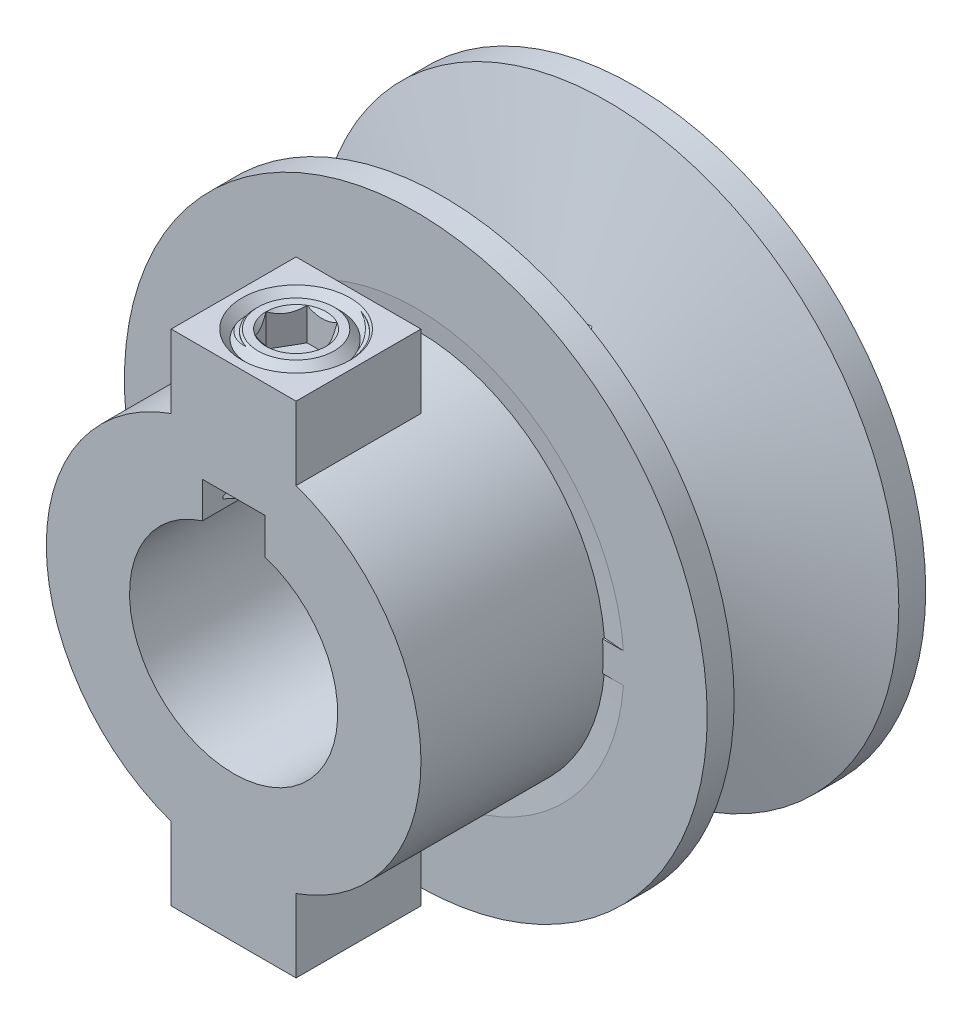
SolidWorks part; units mm, degrees
ref_plane "Front Plane" through (0, 0, 0) normal (0, 0, 1) x (1, 0, 0)
ref_plane "Top Plane" through (0, 0, 0) normal (0, 1, 0) x (1, 0, 0)
ref_plane "Right Plane" through (0, 0, 0) normal (1, 0, 0) x (0, 0, -1)
sketch "Sketch1" plane through (0, 0, 0) normal (1, 0, 0) x (0, 0, -1)
  line L0 (-22.225, 0) -> (8.3312, 0) construction
  line L1 (-6.2793, 22.225) -> (6.2793, 22.225) construction
  line L2 (6.2793, 22.225) -> (8.3312, 22.225)
  line L5 (-8.3312, 22.225) -> (6.2793, 22.225) construction
  line L7 (-22.225, 14.2875) -> (-22.225, -14.2875) construction
  line L10 (-8.3312, 15.875) -> (-8.1923, 14.2875)
  line L13 (-6.2793, 22.225) -> (-2.3965, 9.525)
  line L14 (-2.3965, 9.525) -> (2.3965, 9.525)
  line L15 (2.3965, 9.525) -> (6.2793, 22.225)
  line L16 (8.3312, 7.9375) -> (-22.225, 7.9375) construction
  line L17 (0, 22.225) -> (0, 0) construction
  line L18 (-6.2793, 22.225) -> (-8.3312, 22.225)
  line L20 (-22.225, 0) -> (-22.225, 7.9375) construction
  line L22 (5.3086, 19.05) -> (-5.3086, 19.05) construction
  line L23 (8.3312, 22.225) -> (8.3312, 0) construction
  line L24 (8.3312, 15.875) -> (8.1923, 14.2875)
  line L26 (-22.225, 14.2875) -> (-8.7312, 14.2875)
  line L27 (-8.7312, 14.2875) -> (8.3312, 14.2875) construction
  line L28 (-8.3312, 19.05) -> (-5.3086, 19.05) construction
  line L31 (-22.225, 14.2875) -> (-22.225, 0)
  line L32 (-8.3312, 15.875) -> (-8.3312, 22.225)
  line L33 (8.3312, 22.225) -> (8.3312, 15.875)
  line L34 (-22.225, 0) -> (8.3312, 0)
  line L35 (8.3312, 0) -> (8.3312, 14.2875)
  line L37 (-8.1923, 14.2875) -> (8.1923, 14.2875) construction
  line L39 (-8.7312, 14.2875) -> (-8.1923, 14.2875)
  line L40 (8.3312, 14.2875) -> (8.1923, 14.2875)
  line L42 (-8.7312, 14.2875) -> (-8.7312, 0) construction
  point P6 (0, 14.2875)
  point P16 (0, 9.525)
  point P25 (-8.7312, 0)
  dimension "D1" = 5
revolve "Revolve1" add sketch "Sketch1" angle 360 about L0
sketch "Sketch2" plane through (0, 0, 0) normal (0, 1, 0) x (0, 0, -1)
  line L0 (-6.2793, 22.225) -> (-8.3312, 22.225) construction
  line L1 (-8.3312, 22.225) -> (-8.3312, -22.225) construction
  line L4 (-8.1701, 14.0335) -> (-8.3312, 15.875)
  line L5 (-8.1923, 14.2875) -> (-22.225, 14.2875) construction
  line L6 (-8.3312, 14.0335) -> (-8.1701, 14.0335)
  line L7 (-8.3312, 14.0335) -> (-8.3312, 15.875)
  line L8 (-8.1923, 14.2875) -> (-8.3312, 15.875) construction
  line L11 (8.3312, 14.0335) -> (8.1701, 14.0335)
  line L12 (8.1701, 14.0335) -> (8.3312, 15.875)
  line L13 (0, 0) -> (0, 22.225) construction
  line L14 (8.3312, 14.0335) -> (8.3312, 15.875)
  dimension "D1" = 0.254
extrude "Boss-Extrude1" add sketch "Sketch2" along normal mid plane 2.286
pattern_circular "CirPattern1" count 2 over 360 of "Boss-Extrude1"
sketch "Sketch3" plane through (0, 0, -8.3312) normal (0, 0, -1) x (-1, 0, 0)
  circle A0 centre (0, 0) radius 7.9375
  circle A1 centre (0, 0) radius 19.05 construction
  point P4 (0, 7.9375)
extrude "Cut-Extrude1" cut sketch "Sketch3" against normal up to vertex (30.5562 mm away) up to point (0, 0, 22.225)
sketch "Sketch4" plane through (0, 0, -8.3312) normal (0, 0, -1) x (-1, 0, 0)
  line L0 (2.3812, 7.9375) -> (-2.3812, 7.9375) construction
  line L1 (2.3813, 10.3187) -> (-2.3813, 10.3187)
  line L2 (2.3813, 10.3187) -> (2.3812, 5.5562)
  line L3 (2.3812, 5.5562) -> (-2.3812, 5.5562)
  line L4 (-2.3813, 10.3187) -> (-2.3812, 5.5562)
  dimension "Keyway Wd." = 4.7625
  dimension "Keyway Dp." = 2.3813
extrude "Cut-Extrude2" cut sketch "Sketch4" against normal up to vertex (30.5562 mm away) up to point (0, 0, 22.225)
ref_plane "Plane1" through (0, 14.2875, 0) normal (0, 1, 0) x (-1, 0, 0)
sketch "Sketch5" plane through (0, 14.2875, 0) normal (0, 1, 0) x (-1, 0, 0)
  line L0 (0, 22.225) -> (0, 0) construction
  line L1 (4.7625, 12.7) -> (-4.7625, 12.7)
  line L2 (4.7625, 12.7) -> (4.7625, 22.225)
  line L3 (4.7625, 22.225) -> (-4.7625, 22.225)
  line L4 (-4.7625, 12.7) -> (-4.7625, 22.225)
  line L5 (14.2875, 22.225) -> (-14.2875, 22.225) construction
  dimension "D1" = 9.525
extrude "Boss-Extrude2" add sketch "Sketch5" against normal up to surface (5.5796 mm away) from offset 4.7625
mirror "Mirror1" about plane through (0, 0, 0) normal (0, 1, 0) of "Boss-Extrude2"
sketch "Sketch6" plane through (0, 19.05, 0) normal (0, 1, 0) x (-1, 0, 0)
  line L0 (0, 12.7) -> (0, 22.225) construction
  line L1 (4.7625, 22.225) -> (-4.7625, 22.225) construction
  line L2 (-4.7625, 12.7) -> (4.7625, 12.7) construction
  line L7 (0, 21.4312) -> (0, 20.0201) construction
  circle A0 centre (0, 17.4625) radius 3.9688 construction
  circle A1 centre (0, 17.4625) radius 3.0868
  dimension "D3" = 0.8819
extrude "Cut-Extrude3" cut sketch "Sketch6" against normal up to vertex (19.05 mm away) up to point (0, 0, 22.225)
sketch "Sketch7" plane through (0, 19.05, 0) normal (0, 1, 0) x (-1, 0, 0)
  circle A0 centre (0, 17.4625) radius 3.9688 construction
  circle A1 centre (0, 17.4625) radius 3.9688
  point P3 (0, 21.4312)
curve "Helix/Spiral1" pitch 1.4111 height 15.6986 turns 11.125
sketch "Sketch8" plane through (0, 0, 0) normal (1, 0, 0) x (0, 0, -1)
  line L0 (-20.3619, 20.4611) -> (-20.3619, 19.05) construction
  line L1 (-20.3619, 19.05) -> (-21.584, 19.7556) construction
  line L2 (-21.584, 19.7556) -> (-20.3619, 20.4611) construction
  line L3 (-20.3619, 19.05) -> (-21.4312, 19.05) construction
  line L4 (-21.4312, 19.05) -> (-21.4312, 19.6674) construction
  line L5 (-21.4312, 19.6674) -> (-21.4312, 19.8438) construction
  line L6 (-20.5147, 19.1382) -> (-20.5147, 20.3729) construction
  line L7 (-21.584, 19.7556) -> (-21.4312, 19.7556) construction
  line L8 (-20.5147, 19.7556) -> (-20.3619, 19.7556) construction
  line L9 (-20.4383, 20.417) -> (-20.4383, 19.0941)
  line L10 (-20.4383, 19.0941) -> (-21.4312, 19.6674)
  line L11 (-21.4312, 19.6674) -> (-21.4312, 19.8438)
  line L12 (-21.4312, 19.8438) -> (-20.4383, 20.417)
  point P16 (-20.4383, 19.7556)
  dimension "D1" = 1.4111
  dimension "D2" = 0.1764
sweep "Cut-Sweep1" cut profiles "Sketch8" path "Helix/Spiral1" align with end faces yes
sketch "Sketch9" plane through (0, 19.05, 0) normal (0, 1, 0) x (-1, 0, 0)
  circle A0 centre (0, 17.4625) radius 4.1215
extrude "Cut-Extrude4" cut sketch "Sketch9" against normal through all draft 45
sketch "Sketch10" plane through (0, 0, 0) normal (1, 0, 0) x (0, 0, -1)
  line L0 (-17.4625, 19.05) -> (-17.4625, 9.525) construction
  line L1 (-21.4312, 10.5943) -> (-21.4312, 17.9807)
  line L2 (-17.4625, 19.05) -> (-21.4312, 19.05) construction
  line L3 (-17.4625, 19.05) -> (-17.4625, 9.525)
  line L4 (-17.4625, 9.525) -> (-21.4312, 9.525) construction
  line L5 (-21.4312, 19.05) -> (-21.4312, 9.525) construction
  line L6 (-20.3619, 19.05) -> (-21.4312, 17.9807)
  line L7 (-21.4312, 10.5943) -> (-20.3619, 9.525)
  line L8 (-20.3619, 19.05) -> (-17.4625, 19.05)
  line L9 (-20.3619, 9.525) -> (-17.4625, 9.525)
  line L10 (-12.7, 19.05) -> (-22.225, 19.05) construction
  line L11 (-20.3619, 19.05) -> (-21.4312, 19.05) construction
  line L12 (-21.4312, 19.05) -> (-21.4312, 17.9807) construction
revolve "Revolve3" add sketch "Sketch10" angle 360 about L0
sketch "Sketch11" plane through (0, 19.05, 0) normal (0, 1, 0) x (-1, 0, 0)
  circle A1 centre (0, 17.4625) radius 3.9688
  circle A2 centre (0, 17.4625) radius 3.9688
  dimension "D1" = 0
curve "Helix/Spiral2" pitch 1.4111 height 10.9361 turns 7.75
sketch "Sketch12" plane through (0, 0, 0) normal (1, 0, 0) x (0, 0, -1)
  line L0 (-21.5076, 19.7115) -> (-21.5076, 18.3885)
  line L1 (-21.5076, 19.7556) -> (-21.5076, 19.7115) construction
  line L2 (-21.584, 19.7556) -> (-21.4312, 19.7556) construction
  line L3 (-20.3619, 19.05) -> (-21.584, 19.7556) construction
  line L4 (-21.5076, 19.7115) -> (-20.5147, 19.1382)
  line L5 (-20.5147, 19.1382) -> (-20.5147, 18.9618)
  line L6 (-20.5147, 18.9618) -> (-21.5076, 18.3885)
  line L7 (-21.584, 19.7556) -> (-20.3619, 19.05) construction
  line L8 (-20.3619, 19.05) -> (-21.584, 18.3444) construction
  line L9 (-21.584, 18.3444) -> (-21.584, 19.7556) construction
sweep "Cut-Sweep2" cut profiles "Sketch12" path "Helix/Spiral2" align with end faces yes
sketch "Sketch13" plane through (0, 19.05, 0) normal (0, 1, 0) x (1, 0, 0)
  line L1 (2.2914, -17.4625) -> (1.1457, -15.4781)
  line L2 (1.1457, -15.4781) -> (-1.1457, -15.4781)
  line L3 (-1.1457, -15.4781) -> (-2.2914, -17.4625)
  line L4 (-2.2914, -17.4625) -> (-1.1457, -19.4469)
  line L5 (-1.1457, -19.4469) -> (1.1457, -19.4469)
  line L6 (1.1457, -19.4469) -> (2.2914, -17.4625)
  circle A0 centre (0, -17.4625) radius 1.9844 construction
  dimension "D1" = 3.9688
extrude "Cut-Extrude5" cut sketch "Sketch13" against normal blind 2.4805
sketch "Sketch14" plane through (0, 19.05, 0) normal (0, 1, 0) x (1, 0, 0)
  circle A0 centre (0, -17.4625) radius 2.2914
extrude "Cut-Extrude6" cut sketch "Sketch14" against normal through all draft 45
equation "\"D3@Sketch6\" = \"Screw Pitch@Sketch6\" * 5 / 8"
equation "\"D4@Helix/Spiral1\" = \"Screw Pitch@Sketch6\""
equation "\"D3@Helix/Spiral1\" = \"D4@Helix/Spiral1\" + ( \"Hub Dia.@Sketch1\" / 2 ) "
equation "\"D1@Sketch8\" = \"D4@Helix/Spiral1\""
equation "\"D2@Sketch8\" = \"D1@Sketch8\" / 8"
equation "\"D4@Helix/Spiral2\" = \"D4@Helix/Spiral1\""
equation "\"D3@Helix/Spiral2\" = \"D4@Helix/Spiral2\" + \"Screw Length@Sketch10\""
equation "\"D1@Sketch13\" = \"Screw OD@Sketch6\" / 2"
equation "\"D1@Cut-Extrude5\" = \"D1@Sketch13\" * 5 / 8"
